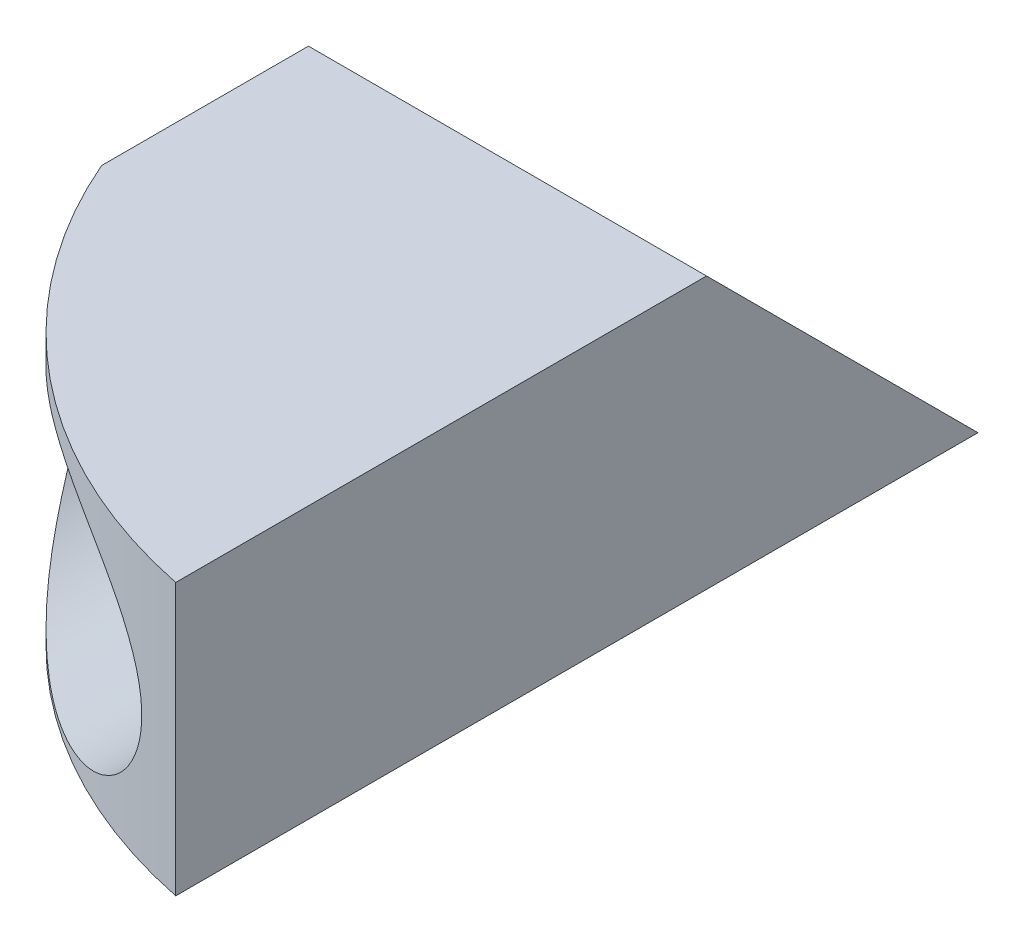
SolidWorks part; units mm, degrees
ref_plane "Front Plane" through (0, 0, 0) normal (0, 0, 1) x (1, 0, 0)
ref_plane "Top Plane" through (0, 0, 0) normal (0, 1, 0) x (1, 0, 0)
ref_plane "Right Plane" through (0, 0, 0) normal (1, 0, 0) x (0, 0, -1)
sketch "Sketch2" plane through (0, 0, 0) normal (1, 0, 0) x (0, 0, -1)
  line L0 (100, 0) -> (70, 30)
  line L1 (0, 0) -> (100, 0)
  line L2 (0, 0) -> (0, 30)
  line L3 (0, 30) -> (70, 30)
  dimension "D1" = 30
  dimension "D2" = 45
  dimension "D3" = 100
extrude "Boss-Extrude2" add sketch "Sketch2" along normal blind 44 contours L2 L3 L0 L1
sketch "Sketch3" plane through (0, 50, -50) normal (0, 0.7071, -0.7071) x (1, 0, 0)
  circle A6 centre (20, 50.7107) radius 19
  dimension "D1" = 38
extrude "Cut-Extrude1" cut sketch "Sketch3" along direction (0, 0, -1) on the side against the normal through all
sketch "Sketch4" plane through (0, 30, 0) normal (0, 1, 0) x (1, 0, 0)
  circle A4 centre (56.3, 71.3884) radius 61.3014
  dimension "D1" = 122.6029
extrude "Cut-Extrude3" cut sketch "Sketch4" against normal through all flip side to cut
